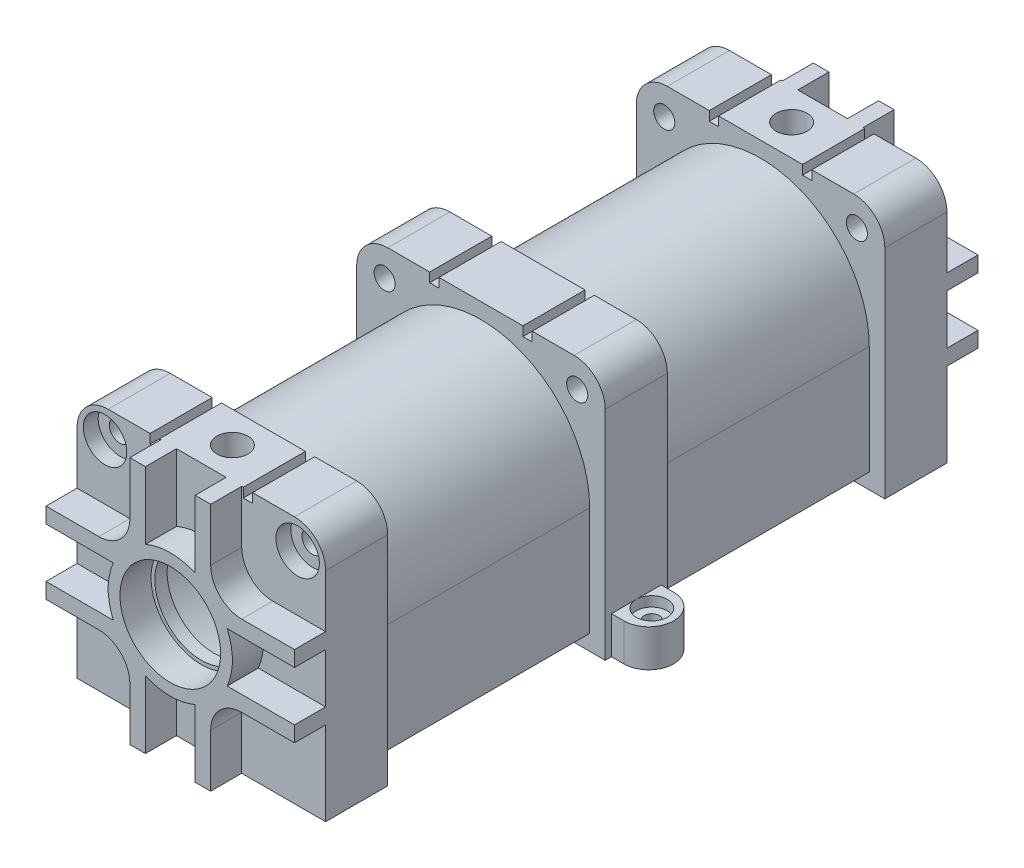
SolidWorks part; units mm, degrees
material "AISI 316 Barra de aço inoxidável recozido (SS)"
ref_plane "Plano frontal" through (0, 0, 0) normal (0, 0, 1) x (1, 0, 0)
ref_plane "Plano superior" through (0, 0, 0) normal (0, 1, 0) x (1, 0, 0)
ref_plane "Plano direito" through (0, 0, 0) normal (1, 0, 0) x (0, 0, -1)
sketch "Esboço1" plane through (0, 0, 0) normal (0, 1, 0) x (1, 0, 0)
  line L1 (20, -50) -> (-20, -50)
  line L2 (20, -50) -> (20, 50)
  line L3 (20, 50) -> (-20, 50)
  line L4 (-20, -50) -> (-20, 50)
  line L5 (20, -50) -> (-20, 50) construction
  line L6 (20, 50) -> (-20, -50) construction
  point P0 (0, 0)
  dimension "D1" = 40
  dimension "D2" = 100
extrude "Ressalto-extrusão1" add sketch "Esboço1" along normal mid plane 40
sketch "Esboço2" plane through (0, 0, 0) normal (0, 0, 1) x (1, 0, 0)
  circle A0 centre (0, 0) radius 16
  dimension "D1" = 32
extrude "Corte-extrusão1" cut sketch "Esboço2" along normal through all and the other way blind 40
sketch "Esboço9" plane through (0, 0, 0) normal (0, 0, 1) x (1, 0, 0)
  line L1 (17.5, -17.5) -> (-17.5, -17.5)
  line L2 (17.5, -17.5) -> (17.5, 0)
  line L4 (-17.5, -17.5) -> (-17.5, 0)
  line L5 (17.5, -17.5) -> (-17.5, 17.5) construction
  line L6 (17.5, 17.5) -> (-17.5, -17.5) construction
  line L10 (-20, -20) -> (20, -20)
  line L11 (20, -20) -> (20, 20)
  line L12 (20, 20) -> (-20, 20)
  line L13 (-20, 20) -> (-20, -20)
  line L14 (-20, -20) -> (20, -20)
  line L15 (20, -20) -> (20, 20)
  line L16 (20, 20) -> (-20, 20)
  line L17 (-20, 20) -> (-20, -20)
  arc A0 (17.5, 0) -> (-17.5, 0) centre (0, 0) ccw
  point P0 (0, 0)
  dimension "D1" = 35
  dimension "D2" = 35
  dimension "D3" = 0
extrude "Corte-extrusão5" cut sketch "Esboço9" against normal blind 35 from offset 5 offset against normal yes
extrude "Corte-extrusão7" cut sketch "Esboço9<4>" along normal blind 35 from offset 5
sketch "Esboço9<4>" plane through (0, 0, 0) normal (0, 0, 1) x (1, 0, 0) same geometry as "Esboço9"
sketch "Esboço3" plane through (0, -20, 0) normal (0, -1, 0) x (1, 0, 0)
  line L0 (20, -50) -> (-20, -50) construction
  line L1 (20, 4) -> (20, -4)
  line L2 (22, 4) -> (20, 4)
  line L3 (25, -50) -> (-25, -50) construction
  line L8 (25, -50) -> (25, 50) construction
  line L9 (25, 50) -> (-25, 50) construction
  line L10 (-25, -50) -> (-25, 50) construction
  line L11 (-20, 50) -> (20, 50) construction
  line L12 (0, -50) -> (0, 50) construction
  line L13 (0, 0) -> (25, 0) construction
  line L14 (25, 0) -> (-25, 0) construction
  line L15 (-20, -4) -> (-22, -4)
  line L17 (-22, 4) -> (-20, 4)
  line L18 (-20, 4) -> (-20, -4)
  line L19 (20, -4) -> (22, -4)
  line L20 (-20, -5) -> (-20, 5) construction
  arc A4 (-22, -4) -> (-22, 4) centre (-22, 0) cw
  arc A5 (22, -4) -> (22, 4) centre (22, 0) ccw
  dimension "D3" = 2
  dimension "D1" = 50
  dimension "D2" = 8
extrude "Ressalto-extrusão2" add sketch "Esboço3" against normal blind 6
hole_wizard "Rebaixo para parafuso de máquina com cabeça panela de M21" positions "Esboço12" profile "Esboço11" counterbore size "M2" standard "Ansi Metric" end condition through all
sketch "Esboço12" plane through (0, -14, 0) normal (0, 1, 0) x (1, 0, 0)
  point P0 (22.5, 0)
  point P2 (-22.5, 0)
  dimension "D1" = 45
  dimension "D2" = 22.5
sketch "Esboço11" plane through (22.5, -14, 0) normal (1, 0, 0) x (0, 0, 1)
  line L0 (0, 0) -> (0, 6)
  line L1 (0, 6) -> (1.2, 6)
  line L3 (1.2, 6) -> (1.2, 1.6)
  line L4 (1.2, 1.6) -> (2.5, 1.6)
  line L5 (2.5, 1.6) -> (2.5, 0)
  line L7 (2.5, 0) -> (0, 0)
  line L11 (0, -6.35) -> (0, 107.95) construction
  dimension "Thru Hole Dia." = 2.4
  dimension "Thru Hole Depth" = 6
  dimension "C'Bore Dia." = 5
  dimension "C'Bore Depth" = 1.6
hole_wizard "Rebaixo para parafuso de máquina com cabeça panela de M31" positions "Esboço14" profile "Esboço15" counterbore size "M3" standard "Ansi Metric" end condition through all
sketch "Esboço14" plane through (0, 0, 50) normal (0, 0, 1) x (1, 0, 0)
  line L1 (15.5, -15.5) -> (-15.5, -15.5)
  line L2 (15.5, -15.5) -> (15.5, 15.5)
  line L3 (15.5, 15.5) -> (-15.5, 15.5)
  line L4 (-15.5, -15.5) -> (-15.5, 15.5)
  line L5 (15.5, -15.5) -> (-15.5, 15.5) construction
  line L6 (15.5, 15.5) -> (-15.5, -15.5) construction
  point P2 (-15.5, 15.5)
  point P126 (15.5, 15.5)
  dimension "D1" = 31
  dimension "D2" = 31
sketch "Esboço15" plane through (-15.5, 15.5, 50) normal (1, 0, 0) x (0, -1, 0)
  line L0 (0, 0) -> (0, 100)
  line L1 (0, 100) -> (1.7, 100)
  line L3 (1.7, 100) -> (1.7, 2.4)
  line L4 (1.7, 2.4) -> (3.5, 2.4)
  line L5 (3.5, 2.4) -> (3.5, 0)
  line L7 (3.5, 0) -> (0, 0)
  line L11 (0, -6.35) -> (0, 107.95) construction
  dimension "Thru Hole Dia." = 3.4
  dimension "Thru Hole Depth" = 100
  dimension "C'Bore Dia." = 7
  dimension "C'Bore Depth" = 2.4
fillet "Filete4" radius 5 6 edges at (20, 20, 45) (-20, 20, 45) (20, 20, 0) (-20, 20, 0) (20, 20, -45) (-20, 20, -45)
hole_wizard "Rebaixo para parafuso de máquina com cabeça panela de M32" positions "Esboço17" profile "Esboço19" counterbore size "M3" standard "Ansi Metric"
sketch "Esboço17" plane through (0, 0, -50) normal (0, 0, -1) x (-1, 0, 0)
  point P0 (-15.5, 15.5)
  point P3 (15.5, 15.5)
sketch "Esboço19" plane through (15.5, 15.5, -50) normal (1, 0, 0) x (0, 1, 0)
  line L0 (0, 0) -> (0, 11.0715)
  line L1 (0, 11.0715) -> (1.7, 10.05)
  line L2 (1.7, 10.05) -> (1.7, 2.4)
  line L3 (1.7, 2.4) -> (3.5, 2.4)
  line L4 (3.5, 2.4) -> (3.5, 0)
  line L5 (3.5, 0) -> (0, 0)
  line L10 (0, 11.0715) -> (-1.7, 10.05) construction
  line L11 (0, -6.35) -> (0, 107.95) construction
  dimension "Hole Dia." = 3.4
  dimension "Hole Depth" = 10.05
  dimension "C'Bore Dia." = 7
  dimension "C'Bore Depth" = 2.4
  dimension "Drill Angle" = 118
sketch "Esboço20" plane through (0, 0, -50) normal (0, 0, -1) x (-1, 0, 0)
  line L0 (0, 20) -> (0, -20) construction
  line L1 (-15, 20) -> (15, 20) construction
  line L2 (-20, -20) -> (20, -20) construction
  line L4 (0.75, 21.5) -> (-0.75, 21.5) construction
  line L5 (0.75, 21.5) -> (0.75, 18.5) construction
  line L6 (0.75, 18.5) -> (-0.75, 18.5) construction
  line L7 (-0.75, 21.5) -> (-0.75, 18.5) construction
  line L8 (0.75, 21.5) -> (-0.75, 18.5) construction
  line L9 (0.75, 18.5) -> (-0.75, 21.5) construction
  line L10 (8.25, 21.5) -> (6.75, 21.5)
  line L11 (8.25, 21.5) -> (8.25, 18.5)
  line L12 (8.25, 18.5) -> (6.75, 18.5)
  line L13 (6.75, 21.5) -> (6.75, 18.5)
  line L14 (8.25, 21.5) -> (6.75, 18.5) construction
  line L15 (8.25, 18.5) -> (6.75, 21.5) construction
  line L16 (-6.75, 21.5) -> (-8.25, 21.5)
  line L17 (-6.75, 21.5) -> (-6.75, 18.5)
  line L18 (-6.75, 18.5) -> (-8.25, 18.5)
  line L19 (-8.25, 21.5) -> (-8.25, 18.5)
  line L20 (-6.75, 21.5) -> (-8.25, 18.5) construction
  line L21 (-6.75, 18.5) -> (-8.25, 21.5) construction
  dimension "D1" = 1.5
  dimension "D2" = 1.5
  dimension "D3" = 2
  dimension "D4" = 2
extrude "Corte-extrusão8" cut sketch "Esboço20" against normal through all
sketch "Esboço21" plane through (0, 20, 0) normal (0, 1, 0) x (1, 0, 0)
  line L0 (0, -50) -> (0, 50) construction
  line L1 (-6.75, -50) -> (6.75, -50) construction
  line L2 (6.75, 50) -> (-6.75, 50) construction
  line L3 (20, 45) -> (-20, 45) construction
  line L4 (20, 50) -> (20, 40) construction
  line L5 (-20, 40) -> (-20, 50) construction
  line L6 (20, -45) -> (-20, -45) construction
  line L7 (20, -40) -> (20, -50) construction
  line L8 (-20, -50) -> (-20, -40) construction
  circle A0 centre (0, -45) radius 2.5006
  circle A1 centre (0, 45) radius 2.5006
  dimension "D1" = 5.0012
extrude "Corte-extrusão9" cut sketch "Esboço21" against normal blind 5
sketch "Esboço22" plane through (0, 0, -50) normal (0, 0, -1) x (-1, 0, 0)
  line L0 (0, 20) -> (0, -20) construction
  line L1 (-6.75, 20) -> (6.75, 20) construction
  line L2 (-20, -20) -> (20, -20) construction
  line L3 (20, 0) -> (-20, 0) construction
  line L4 (20, 15) -> (20, -20) construction
  line L5 (-20, 15) -> (-20, -20) construction
  line L6 (-6.5, 20) -> (-6.5, 11.5)
  line L7 (-11.5, 6.5) -> (-20, 6.5)
  line L8 (-4, 20) -> (-4, 9.1652)
  line L9 (-9.1652, 4) -> (-20, 4)
  line L10 (-20, 4) -> (-20, 6.5)
  line L11 (-6.5, 20) -> (-4, 20)
  line L12 (-6.5, 20) -> (-6.5, 6.5) construction
  line L13 (-6.5, 6.5) -> (-20, 6.5) construction
  line L14 (6.5, 20) -> (6.5, 11.5)
  line L15 (11.5, 6.5) -> (20, 6.5)
  line L16 (20, 4) -> (20, 6.5)
  line L17 (9.1652, 4) -> (20, 4)
  line L18 (4, 20) -> (4, 9.1652)
  line L19 (6.5, 20) -> (4, 20)
  line L20 (6.5, -20) -> (4, -20)
  line L21 (4, -20) -> (4, -9.1652)
  line L22 (9.1652, -4) -> (20, -4)
  line L23 (20, -4) -> (20, -6.5)
  line L24 (11.5, -6.5) -> (20, -6.5)
  line L25 (6.5, -20) -> (6.5, -11.5)
  line L26 (-6.5, -20) -> (-6.5, -11.5)
  line L27 (-11.5, -6.5) -> (-20, -6.5)
  line L28 (-20, -4) -> (-20, -6.5)
  line L29 (-9.1652, -4) -> (-20, -4)
  line L30 (-4, -20) -> (-4, -9.1652)
  line L31 (-6.5, -20) -> (-4, -20)
  line L33 (-4, 20) -> (-4, 4) construction
  line L34 (-4, 4) -> (-20, 4) construction
  arc A0 (-9.1652, 4) -> (-9.1652, -4) centre (0, 0) ccw
  arc A1 (-6.5, 11.5) -> (-11.5, 6.5) centre (-11.5, 11.5) cw
  arc A2 (6.5, 11.5) -> (11.5, 6.5) centre (11.5, 11.5) ccw
  arc A3 (6.5, -11.5) -> (11.5, -6.5) centre (11.5, -11.5) cw
  arc A4 (-6.5, -11.5) -> (-11.5, -6.5) centre (-11.5, -11.5) ccw
  arc A5 (-4, -9.1652) -> (4, -9.1652) centre (0, 0) ccw
  arc A6 (9.1652, -4) -> (9.1652, 4) centre (0, 0) ccw
  arc A7 (4, 9.1652) -> (-4, 9.1652) centre (0, 0) ccw
  point P26 (-6.5, 6.5)
  dimension "D1" = 20
  dimension "D7" = 5
  dimension "D3" = 6.5
  dimension "D4" = 6.5
  dimension "D2" = 2.5
extrude "Ressalto-extrusão3" add sketch "Esboço22" along normal blind 5
sketch "Esboço23" plane through (0, 0, -55) normal (0, 0, -1) x (-1, 0, 0)
  circle A0 centre (0, 0) radius 10
  arc A1 (4, 9.1652) -> (-4, 9.1652) centre (0, 0) ccw construction
extrude "Ressalto-extrusão4" add sketch "Esboço23" along normal blind 2
fillet "Filete5" radius 2 1 edges at (-10, 0, -57)
sketch "Esboço24" plane through (0, 0, 50) normal (0, 0, 1) x (1, 0, 0)
  circle A0 centre (0, 0) radius 16 construction
  circle A1 centre (0, 0) radius 16
  circle A2 centre (0, 0) radius 7.5
  dimension "D1" = 15
extrude "Ressalto-extrusão5" add sketch "Esboço24" against normal blind 2
mirror "Espelhar1" about plane through (0, 0, 0) normal (0, 0, 1) of "Ressalto-extrusão3"
sketch "Esboço26" plane through (0, 0, 55) normal (0, 0, 1) x (1, 0, 0)
  circle A0 centre (0, 0) radius 8.1
  dimension "D1" = 16.2
extrude "Corte-extrusão10" cut sketch "Esboço26" against normal blind 5
equation "\"D3@Esboço22\"=\"D4@Esboço22\""
